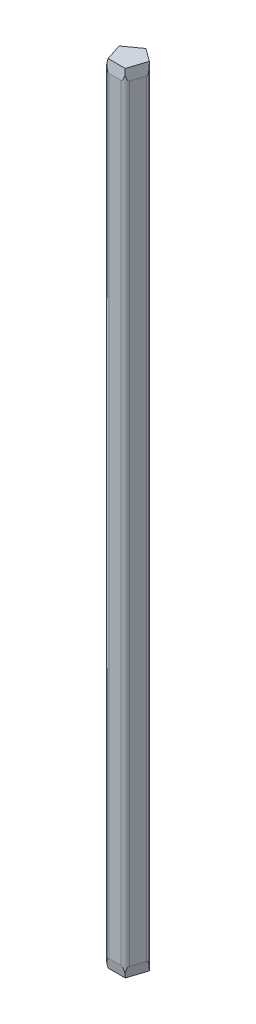
SolidWorks part; units mm, degrees
ref_plane "Front Plane" through (0, 0, 0) normal (0, 0, 1) x (1, 0, 0)
ref_plane "Top Plane" through (0, 0, 0) normal (0, 1, 0) x (1, 0, 0)
ref_plane "Right Plane" through (0, 0, 0) normal (1, 0, 0) x (0, 0, -1)
sketch "Sketch1" plane through (0, 0, 0) normal (0, 1, 0) x (1, 0, 0)
  line L1 (0, 6.4437) -> (-6.1283, 1.9912)
  line L2 (-6.1283, 1.9912) -> (-3.7875, -5.213)
  line L3 (-3.7875, -5.213) -> (3.7875, -5.213)
  line L4 (3.7875, -5.213) -> (6.1283, 1.9912)
  line L5 (6.1283, 1.9912) -> (0, 6.4437)
  circle A0 centre (0, 0) radius 5.213 construction
  dimension "D1" = 7.575
extrude "Boss-Extrude1" add sketch "Sketch1" along normal blind 300
chamfer "Chamfer1" distance 4 angle 10 8 edges at (4.9579, 300, 1.6109) (0, 300, 5.213) (-4.9579, 300, 1.6109) (-3.0642, 300, -4.2174) (4.9579, 0, 1.6109) (0, 0, 5.213) (-4.9579, 0, 1.6109) (-3.0642, 0, -4.2174) first distance on face at (4.9579, 150, 1.6109) first distance on face at (0, 150, 5.213) first distance on face at (-4.9579, 150, 1.6109) first distance on face at (-3.0642, 150, -4.2174)
ref_axis "Axis1" through (0, 315, 0) along (0, -1, 0)
fillet "Fillet2" radius 1.9 2 edges at (3.7875, 150, 5.213) (-6.1283, 150, -1.9912)
fillet "Fillet3" radius 1.3 2 edges at (6.1283, 150, -1.9912) (0, 150, -6.4437)
fillet "Fillet4" radius 2.2 1 edges at (-3.7875, 150, 5.213)
